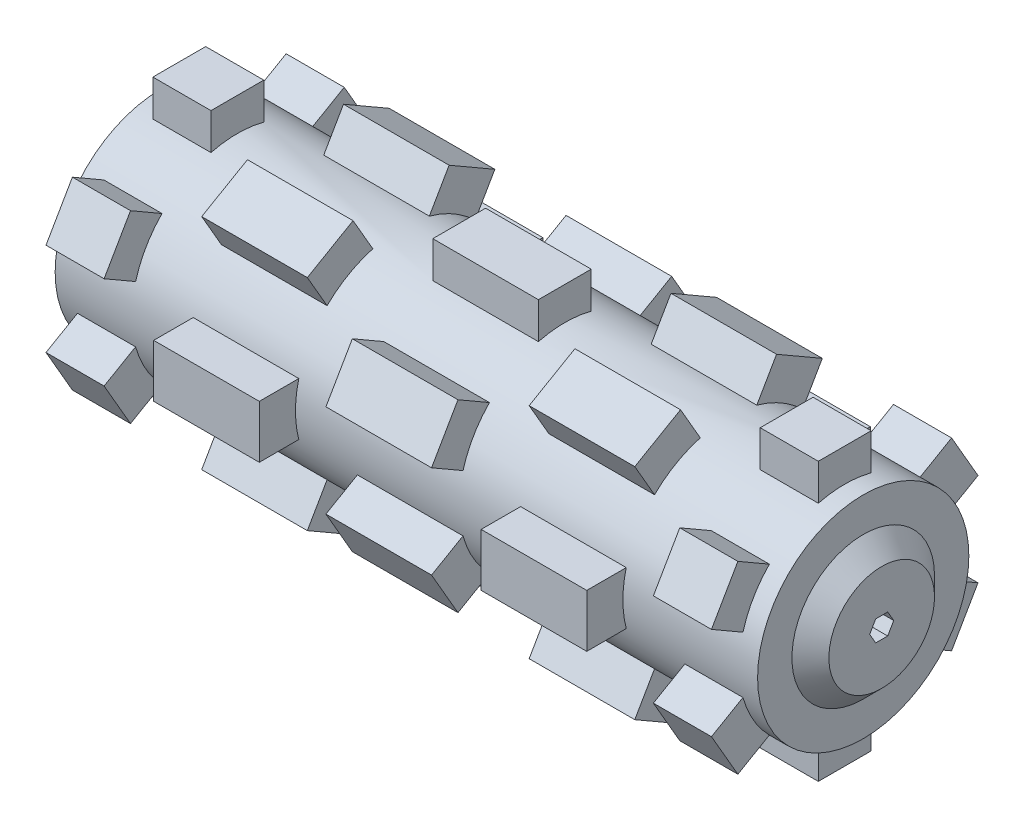
SolidWorks part; units mm, degrees
material "AISI 304"
ref_plane "Front Plane" through (0, 0, 0) normal (0, 0, 1) x (1, 0, 0)
ref_plane "Top Plane" through (0, 0, 0) normal (0, 1, 0) x (1, 0, 0)
ref_plane "Right Plane" through (0, 0, 0) normal (1, 0, 0) x (0, 0, -1)
sketch "Sketch1" plane through (0, 0, 0) normal (1, 0, 0) x (0, 0, -1)
  line L0 (0, -34.925) -> (0, 34.925) construction
  line L1 (-12.7, 66.675) -> (12.7, 66.675)
  line L2 (-12.7, 66.675) -> (-12.7, 34.925)
  line L3 (-12.7, 34.925) -> (12.7, 34.925)
  line L4 (12.7, 66.675) -> (12.7, 34.925)
  line L5 (-12.7, 66.675) -> (12.7, 34.925) construction
  line L6 (-12.7, 34.925) -> (12.7, 66.675) construction
  line L7 (51.3922, 44.336) -> (23.8959, 28.461)
  line L8 (51.3922, 44.336) -> (64.0922, 22.339)
  line L9 (64.0922, 22.339) -> (36.5959, 6.464)
  line L10 (23.8959, 28.461) -> (36.5959, 6.464)
  line L11 (64.0922, -22.339) -> (36.5959, -6.464)
  line L12 (64.0922, -22.339) -> (51.3922, -44.336)
  line L13 (51.3922, -44.336) -> (23.8959, -28.461)
  line L14 (36.5959, -6.464) -> (23.8959, -28.461)
  line L15 (12.7, -66.675) -> (12.7, -34.925)
  line L16 (12.7, -66.675) -> (-12.7, -66.675)
  line L17 (-12.7, -66.675) -> (-12.7, -34.925)
  line L18 (12.7, -34.925) -> (-12.7, -34.925)
  line L19 (-51.3922, -44.336) -> (-23.8959, -28.461)
  line L20 (-51.3922, -44.336) -> (-64.0922, -22.339)
  line L21 (-64.0922, -22.339) -> (-36.5959, -6.464)
  line L22 (-23.8959, -28.461) -> (-36.5959, -6.464)
  line L23 (-64.0922, 22.339) -> (-36.5959, 6.464)
  line L24 (-64.0922, 22.339) -> (-51.3922, 44.336)
  line L25 (-51.3922, 44.336) -> (-23.8959, 28.461)
  line L26 (-36.5959, 6.464) -> (-23.8959, 28.461)
  circle A0 centre (0, 0) radius 50.8
  point P3 (0, 50.8)
  point P10 (0, 0)
  point P14 (0, 0)
  point P34 (0, 0)
  dimension "D1" = 101.6
  dimension "D3" = 25.4
  dimension "D4" = 31.75
  dimension "D2" = 6
extrude "Boss-Extrude3" add sketch "Sketch1" along normal blind 50.8 contours A0 | L2 L1 L4 L3 | L23 L26 L25 L24 | L19 L22 L21 L20 | L15 L18 L17 L16 | L11 L14 L13 L12 | L7 L10 L9 L8
sketch "Sketch2" plane through (50.8, 0, 0) normal (1, 0, 0) x (0, 0, -1)
  circle A0 centre (0, 0) radius 50.8
extrude "Boss-Extrude4" add sketch "Sketch2" along normal blind 27.94
sketch "Sketch3" plane through (78.74, 0, 0) normal (1, 0, 0) x (0, 0, -1)
  line L0 (0, 0) -> (12.7, 66.675) construction
  line L1 (12.7, 66.675) -> (12.7, 49.1869) construction
  line L2 (36.4373, 12.7) -> (36.4373, 0)
  line L3 (51.3922, 44.336) -> (0, 0) construction
  line L4 (34.0936, 59.0519) -> (0, 0) construction
  line L5 (18.2186, 31.5556) -> (29.2172, 25.2056)
  line L6 (29.2172, 25.2056) -> (45.0922, 52.7019)
  line L7 (45.0922, 52.7019) -> (23.0951, 65.4019)
  line L8 (23.0951, 65.4019) -> (7.2201, 37.9056)
  line L9 (7.2201, 37.9056) -> (18.2186, 31.5556)
  line L10 (36.4373, 0) -> (36.4373, -12.7)
  line L11 (36.4373, -12.7) -> (68.1873, -12.7)
  line L12 (68.1873, -12.7) -> (68.1873, 12.7)
  line L13 (68.1873, 12.7) -> (36.4373, 12.7)
  line L14 (29.2172, -25.2056) -> (18.2186, -31.5556)
  line L15 (18.2186, -31.5556) -> (7.2201, -37.9056)
  line L16 (7.2201, -37.9056) -> (23.0951, -65.4019)
  line L17 (23.0951, -65.4019) -> (45.0922, -52.7019)
  line L18 (45.0922, -52.7019) -> (29.2172, -25.2056)
  line L19 (-7.2201, -37.9056) -> (-18.2186, -31.5556)
  line L20 (-18.2186, -31.5556) -> (-29.2172, -25.2056)
  line L21 (-29.2172, -25.2056) -> (-45.0922, -52.7019)
  line L22 (-45.0922, -52.7019) -> (-23.0951, -65.4019)
  line L23 (-23.0951, -65.4019) -> (-7.2201, -37.9056)
  line L24 (-36.4373, -12.7) -> (-36.4373, 0)
  line L25 (-36.4373, 0) -> (-36.4373, 12.7)
  line L26 (-36.4373, 12.7) -> (-68.1873, 12.7)
  line L27 (-68.1873, 12.7) -> (-68.1873, -12.7)
  line L28 (-68.1873, -12.7) -> (-36.4373, -12.7)
  line L29 (-29.2172, 25.2056) -> (-18.2186, 31.5556)
  line L30 (-18.2186, 31.5556) -> (-7.2201, 37.9056)
  line L31 (-7.2201, 37.9056) -> (-23.0951, 65.4019)
  line L32 (-23.0951, 65.4019) -> (-45.0922, 52.7019)
  line L33 (-45.0922, 52.7019) -> (-29.2172, 25.2056)
  circle A0 centre (0, 0) radius 50.8
  circle A1 centre (0, 0) radius 67.8737 construction
  point P44 (0, 0)
  dimension "D1" = 31.75
  dimension "D2" = 25.4
  dimension "D3" = 6
extrude "Boss-Extrude5" add sketch "Sketch3" along normal blind 50.8 contours A0 | L24 L25 L26 L27 L28 | L29 L30 L31 L32 L33 | L9 L5 L6 L7 L8 | L2 L10 L11 L12 L13 | L14 L15 L16 L17 L18 | L19 L20 L21 L22 L23
sketch "Sketch4" plane through (129.54, 0, 0) normal (1, 0, 0) x (0, 0, -1)
  circle A0 centre (0, 0) radius 50.8
extrude "Boss-Extrude6" add sketch "Sketch4" along normal blind 27.94
sketch "Sketch5" plane through (157.48, 0, 0) normal (1, 0, 0) x (0, 0, -1)
  line L0 (12.7, 66.675) -> (12.7, 49.1869) construction
  line L1 (-12.7, 66.675) -> (12.7, 66.675)
  line L2 (-12.7, 66.675) -> (-12.7, 34.925)
  line L3 (-12.7, 34.925) -> (12.7, 34.925)
  line L4 (12.7, 66.675) -> (12.7, 34.925)
  line L5 (51.3922, 44.336) -> (23.8959, 28.461)
  line L6 (51.3922, 44.336) -> (64.0922, 22.339)
  line L7 (64.0922, 22.339) -> (36.5959, 6.464)
  line L8 (23.8959, 28.461) -> (36.5959, 6.464)
  line L9 (64.0922, -22.339) -> (36.5959, -6.464)
  line L10 (64.0922, -22.339) -> (51.3922, -44.336)
  line L11 (51.3922, -44.336) -> (23.8959, -28.461)
  line L12 (36.5959, -6.464) -> (23.8959, -28.461)
  line L13 (12.7, -66.675) -> (12.7, -34.925)
  line L14 (12.7, -66.675) -> (-12.7, -66.675)
  line L15 (-12.7, -66.675) -> (-12.7, -34.925)
  line L16 (12.7, -34.925) -> (-12.7, -34.925)
  line L17 (-51.3922, -44.336) -> (-23.8959, -28.461)
  line L18 (-51.3922, -44.336) -> (-64.0922, -22.339)
  line L19 (-64.0922, -22.339) -> (-36.5959, -6.464)
  line L20 (-23.8959, -28.461) -> (-36.5959, -6.464)
  line L21 (-64.0922, 22.339) -> (-36.5959, 6.464)
  line L22 (-64.0922, 22.339) -> (-51.3922, 44.336)
  line L23 (-51.3922, 44.336) -> (-23.8959, 28.461)
  line L24 (-36.5959, 6.464) -> (-23.8959, 28.461)
  circle A0 centre (0, 0) radius 50.8
  point P33 (0, 0)
  dimension "D1" = 31.75
  dimension "D2" = 25.4
  dimension "D3" = 6
extrude "Boss-Extrude7" add sketch "Sketch5" along normal blind 27.94 contours A0 | L21 L24 L23 L22 | L2 L1 L4 L3 | L5 L8 L7 L6 | L17 L20 L19 L18 | L13 L16 L15 L14 | L9 L12 L11 L10
sketch "Sketch6" plane through (0, 0, 0) normal (-1, 0, 0) x (0, 0, 1)
  circle A0 centre (0, 0) radius 50.8
extrude "Boss-Extrude8" add sketch "Sketch6" along normal blind 27.94
sketch "Sketch7" plane through (-27.94, 0, 0) normal (-1, 0, 0) x (0, 0, 1)
  line L0 (23.0951, 65.4019) -> (45.0922, 52.7019)
  line L1 (45.0922, 52.7019) -> (29.2172, 25.2056)
  line L2 (29.2172, 25.2056) -> (7.2201, 37.9056)
  line L3 (7.2201, 37.9056) -> (23.0951, 65.4019)
  line L4 (36.4373, 12.7) -> (68.1873, 12.7)
  line L5 (68.1873, 12.7) -> (68.1873, -12.7)
  line L6 (68.1873, -12.7) -> (36.4373, -12.7)
  line L7 (36.4373, -12.7) -> (36.4373, 12.7)
  line L8 (29.2172, -25.2056) -> (45.0922, -52.7019)
  line L9 (45.0922, -52.7019) -> (23.0951, -65.4019)
  line L10 (23.0951, -65.4019) -> (7.2201, -37.9056)
  line L11 (7.2201, -37.9056) -> (29.2172, -25.2056)
  line L12 (-7.2201, -37.9056) -> (-23.0951, -65.4019)
  line L13 (-23.0951, -65.4019) -> (-45.0922, -52.7019)
  line L14 (-45.0922, -52.7019) -> (-29.2172, -25.2056)
  line L15 (-29.2172, -25.2056) -> (-7.2201, -37.9056)
  line L16 (-36.4373, -12.7) -> (-68.1873, -12.7)
  line L17 (-68.1873, -12.7) -> (-68.1873, 12.7)
  line L18 (-68.1873, 12.7) -> (-36.4373, 12.7)
  line L19 (-36.4373, 12.7) -> (-36.4373, -12.7)
  line L20 (-29.2172, 25.2056) -> (-45.0922, 52.7019)
  line L21 (-45.0922, 52.7019) -> (-23.0951, 65.4019)
  line L22 (-23.0951, 65.4019) -> (-7.2201, 37.9056)
  line L23 (-7.2201, 37.9056) -> (-29.2172, 25.2056)
  circle A0 centre (0, 0) radius 50.8
  point P28 (0, 0)
  dimension "D1" = 25.4
  dimension "D2" = 31.75
  dimension "D3" = 6
extrude "Boss-Extrude9" add sketch "Sketch7" along normal blind 50.8 contours L3 L0 L1 L2 | L20 L21 L22 L23 | A0 | L16 L17 L18 L19 | L12 L13 L14 L15 | L8 L9 L10 L11 | L4 L5 L6 L7
sketch "Sketch8" plane through (-78.74, 0, 0) normal (-1, 0, 0) x (0, 0, 1)
  circle A0 centre (0, 0) radius 50.8
extrude "Boss-Extrude10" add sketch "Sketch8" along normal blind 27.94
sketch "Sketch9" plane through (-106.68, 0, 0) normal (-1, 0, 0) x (0, 0, 1)
  line L0 (12.7, 66.675) -> (12.7, 49.1869) construction
  line L1 (-12.7, 66.675) -> (12.7, 66.675)
  line L2 (-12.7, 66.675) -> (-12.7, 34.925)
  line L3 (-12.7, 34.925) -> (12.7, 34.925)
  line L4 (12.7, 66.675) -> (12.7, 34.925)
  line L5 (51.3922, 44.336) -> (23.8959, 28.461)
  line L6 (51.3922, 44.336) -> (64.0922, 22.339)
  line L7 (64.0922, 22.339) -> (36.5959, 6.464)
  line L8 (23.8959, 28.461) -> (36.5959, 6.464)
  line L9 (64.0922, -22.339) -> (36.5959, -6.464)
  line L10 (64.0922, -22.339) -> (51.3922, -44.336)
  line L11 (51.3922, -44.336) -> (23.8959, -28.461)
  line L12 (36.5959, -6.464) -> (23.8959, -28.461)
  line L13 (12.7, -66.675) -> (12.7, -34.925)
  line L14 (12.7, -66.675) -> (-12.7, -66.675)
  line L15 (-12.7, -66.675) -> (-12.7, -34.925)
  line L16 (12.7, -34.925) -> (-12.7, -34.925)
  line L17 (-51.3922, -44.336) -> (-23.8959, -28.461)
  line L18 (-51.3922, -44.336) -> (-64.0922, -22.339)
  line L19 (-64.0922, -22.339) -> (-36.5959, -6.464)
  line L20 (-23.8959, -28.461) -> (-36.5959, -6.464)
  line L21 (-64.0922, 22.339) -> (-36.5959, 6.464)
  line L22 (-64.0922, 22.339) -> (-51.3922, 44.336)
  line L23 (-51.3922, 44.336) -> (-23.8959, 28.461)
  line L24 (-36.5959, 6.464) -> (-23.8959, 28.461)
  circle A0 centre (0, 0) radius 50.8
  point P33 (0, 0)
  dimension "D1" = 31.75
  dimension "D2" = 25.4
  dimension "D3" = 6
extrude "Boss-Extrude11" add sketch "Sketch9" along normal blind 27.94 contours A0 | L21 L24 L23 L22 | L17 L20 L19 L18 | L13 L16 L15 L14 | L9 L12 L11 L10 | L5 L8 L7 L6 | L2 L1 L4 L3
sketch "Sketch10" plane through (185.42, 0, 0) normal (1, 0, 0) x (0, 0, -1)
  circle A0 centre (0, 0) radius 50.8
extrude "Boss-Extrude12" add sketch "Sketch10" along normal blind 8.89
sketch "Sketch11" plane through (-134.62, 0, 0) normal (-1, 0, 0) x (0, 0, 1)
  circle A0 centre (0, 0) radius 50.8
extrude "Boss-Extrude13" add sketch "Sketch11" along normal blind 8.89
sketch "Sketch12" plane through (194.31, 0, 0) normal (1, 0, 0) x (0, 0, -1)
  circle A1 centre (0, 0) radius 25.4
  dimension "D2" = 50.8
extrude "Boss-Extrude14" add sketch "Sketch12" along normal blind 8.89
sketch "Sketch13" plane through (-143.51, 0, 0) normal (-1, 0, 0) x (0, 0, 1)
  circle A0 centre (0, 0) radius 25.4
  dimension "D1" = 50.8
extrude "Boss-Extrude15" add sketch "Sketch13" along normal blind 8.89
sketch "Sketch14" plane through (-152.4, 0, 0) normal (-1, 0, 0) x (0, 0, 1)
  line L1 (5.7735, 0) -> (2.8868, 5)
  line L2 (2.8868, 5) -> (-2.8868, 5)
  line L3 (-2.8868, 5) -> (-5.7735, 0)
  line L4 (-5.7735, 0) -> (-2.8868, -5)
  line L5 (-2.8868, -5) -> (2.8868, -5)
  line L6 (2.8868, -5) -> (5.7735, 0)
  circle A0 centre (0, 0) radius 5
  circle A1 centre (0, 0) radius 5 construction
  point P3 (0, 0)
  dimension "D1" = 10
extrude "Cut-Extrude1" cut sketch "Sketch14" against normal through all contours A0 L3 L4 | A0 | A0 L2 L3 | A0 L1 L2 | A0 L6 L1 | A0 L5 L6 | A0 L4 L5 region at (-152.4, 0, 5.1678) region at (-152.4, 4.4755, 2.5839) region at (-152.4, 0, 0) region at (-152.4, -4.4755, 2.5839) region at (-152.4, 4.4755, -2.5839) region at (-152.4, -4.4755, -2.5839) region at (-152.4, 0, -5.1678)
chamfer "Chamfer3" distance 8.89 angle 45 2 edges at (-143.51, 0, 25.4) (194.31, 0, -25.4)
